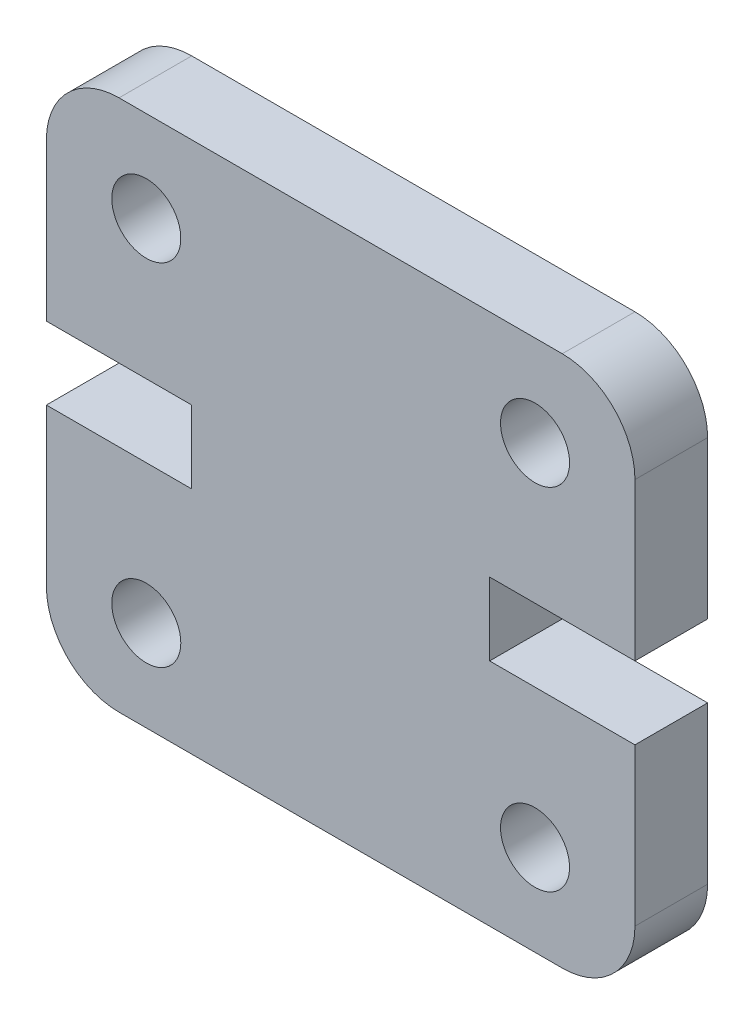
SolidWorks part; units mm, degrees
ref_plane "Front Plane" through (0, 0, 0) normal (0, 0, 1) x (1, 0, 0)
ref_plane "Top Plane" through (0, 0, 0) normal (0, 1, 0) x (1, 0, 0)
ref_plane "Right Plane" through (0, 0, 0) normal (1, 0, 0) x (0, 0, -1)
sketch "Sketch1" plane through (0, 0, 0) normal (0, 0, 1) x (1, 0, 0)
  line L0 (8.1, 14.645) -> (8.1, 0) construction
  line L1 (0, 7.3225) -> (16.2, 7.3225) construction
  line L2 (2, 14.645) -> (14.2, 14.645)
  line L3 (0, 8.3225) -> (4, 8.3225)
  line L4 (0, 8.3225) -> (0, 12.645)
  line L5 (12.2, 6.3225) -> (12.2, 8.3225)
  line L6 (16.2, 6.3225) -> (12.2, 6.3225)
  line L7 (16.2, 6.3225) -> (16.2, 2)
  line L8 (16.2, 8.3225) -> (16.2, 12.645)
  line L9 (16.2, 8.3225) -> (12.2, 8.3225)
  line L12 (0, 6.3225) -> (0, 2)
  line L17 (0, 6.3225) -> (4, 6.3225)
  line L18 (4, 6.3225) -> (4, 8.3225)
  line L19 (2, 0) -> (14.2, 0)
  circle A0 centre (2.75, 12.145) radius 0.95
  arc A1 (0, 12.645) -> (2, 14.645) centre (2, 12.645) cw
  circle A2 centre (13.45, 2.5) radius 0.95
  arc A3 (16.2, 2) -> (14.2, 0) centre (14.2, 2) cw
  arc A4 (16.2, 12.645) -> (14.2, 14.645) centre (14.2, 12.645) ccw
  circle A5 centre (13.45, 12.145) radius 0.95
  arc A11 (0, 2) -> (2, 0) centre (2, 2) ccw
  circle A13 centre (2.75, 2.5) radius 0.95
  point P9 (4, 7.3225)
  point P14 (8.1, 7.3225)
  point P27 (12.2, 7.3225)
  dimension "D2" = 2
  dimension "D8" = 1.9
  dimension "D3" = 2.75
  dimension "D4" = 8.1
  dimension "D5" = 2.5
  dimension "D1" = 1
  dimension "D7" = 4
  dimension "D6" = 6.3225
extrude "Boss-Extrude1" add sketch "Sketch1" along normal blind 4
sketch "Sketch2" plane through (0, 0, 0) normal (0, 0, -1) x (-1, 0, 0)
  line L0 (0, 0) -> (-16.2, 0)
  line L1 (-16.2, 0) -> (-16.2, 14.645)
  line L2 (-16.2, 14.645) -> (0, 14.645)
  line L3 (0, 14.645) -> (0, 0)
extrude "Cut-Extrude1" cut sketch "Sketch2" against normal blind 2
equation "\"D4@Sketch1\"= \"fingerWidth@parametersSketch@prostheticParameters.SLDPRT\" / 2'MIP width"
equation "\"D6@Sketch1\"=( \"HL@parametersSketch@prostheticParameters.SLDPRT\" * 0.117 - 4 - 3 - 2) / 2 'MIP length - Sil. Sht DIP - Sil. Sht MIP"
equation "\"D8@Sketch1\"= 1.5 + \"tol1@parametersSketch@prostheticParameters.SLDPRT\""
